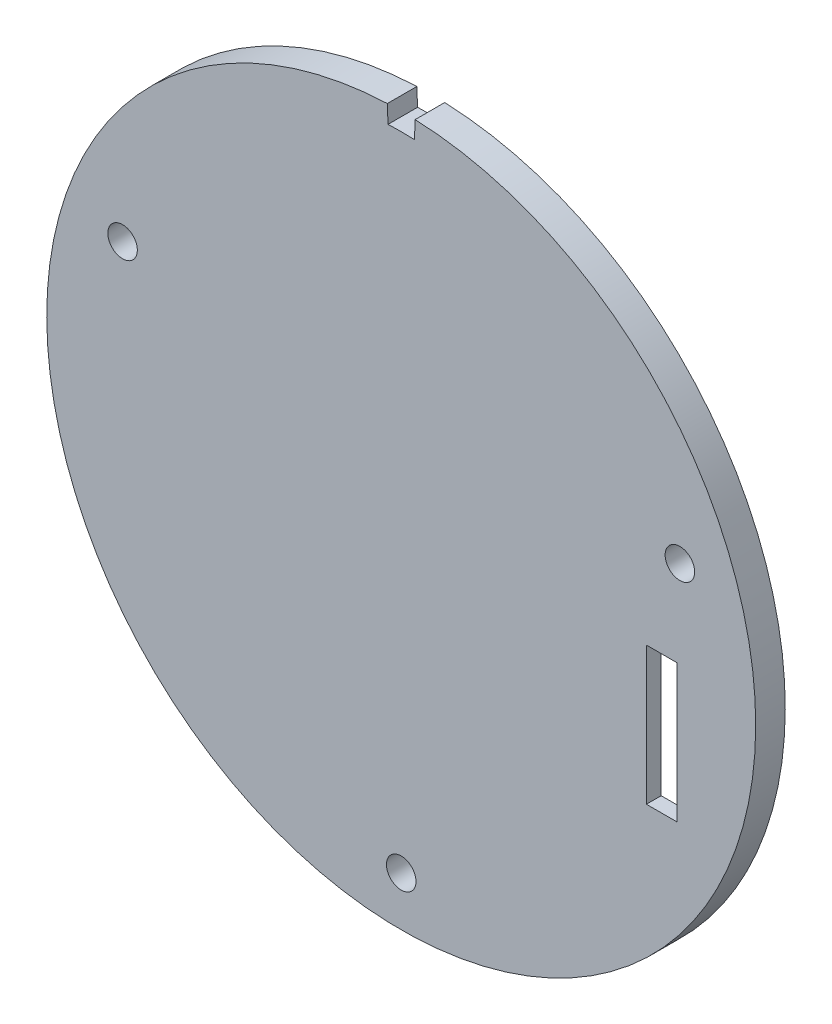
SolidWorks part; units mm, degrees
material "PMMA"
ref_plane "Front Plane" through (0, 0, 0) normal (0, 0, 1) x (1, 0, 0)
ref_plane "Top Plane" through (0, 0, 0) normal (0, 1, 0) x (1, 0, 0)
ref_plane "Right Plane" through (0, 0, 0) normal (1, 0, 0) x (0, 0, -1)
sketch "Sketch1" plane through (0, 0, 0) normal (0, 0, 1) x (1, 0, 0)
  line L0 (0, 45.9969) -> (0, -49.8146) construction
  line L1 (-28, 4.5) -> (28, 4.5)
  line L2 (28, 4.5) -> (28, -17)
  line L3 (28, -17) -> (21.5, -23.5)
  line L4 (21.5, -23.5) -> (-21.5, -23.5)
  line L5 (-21.5, -23.5) -> (-28, -17)
  line L6 (-28, -17) -> (-28, 4.5)
  line L7 (-1.4134, 35.9722) -> (-1.3427, 34.1736)
  line L8 (28, 1.5) -> (24.9, 1.5)
  line L9 (1.3427, 34.1736) -> (1.4134, 35.9722)
  line L10 (24.9, 1.5) -> (24.9, -12.5)
  line L11 (24.9, -12.5) -> (28, -12.5)
  line L12 (28.3, 10.3761) -> (-28.3, 10.3761) construction
  line L14 (23.5, -21.6239) -> (-23.5, -21.6239) construction
  line L15 (23.5, -21.6239) -> (23.5, 25.3761) construction
  line L16 (23.5, 25.3761) -> (-23.5, 25.3761) construction
  line L17 (-23.5, -21.6239) -> (-23.5, 25.3761) construction
  line L18 (23.5, -21.6239) -> (-23.5, 25.3761) construction
  line L19 (23.5, 25.3761) -> (-23.5, -21.6239) construction
  arc A0 (-1.4134, 35.9722) -> (1.4134, 35.9722) centre (0, 0) ccw
  arc A1 (-1.3427, 34.1736) -> (1.3427, 34.1736) centre (0, 0) cw
  circle A2 centre (28.3, 10.3761) radius 1.5
  circle A3 centre (-28.3, 10.3761) radius 1.5
  circle A4 centre (0, -31) radius 1.5
  point P22 (0, 1.8761)
  point P27 (-1.2692, -29.9126)
  dimension "D1" = 72
  dimension "D9" = 34.2
  dimension "D10" = 3
  dimension "D13" = 3
  dimension "D14" = 3
  dimension "D18" = 3
  dimension "D19" = 31
  dimension "D2" = 56
  dimension "D3" = 21.5
  dimension "D4" = 135
  dimension "D5" = 28
  dimension "D6" = 135
  dimension "D7" = 4.5
  dimension "D8" = 4.5
  dimension "D11" = 17
  dimension "D12" = 3.1
  dimension "D15" = 47
  dimension "D16" = 47
  dimension "D17" = 15
extrude "Boss-Extrude3" add sketch "Sketch1" against normal blind 3 contours A1 L0 L1 L2 L3 L4 A0 L9 | L0 A1 L7 A0 L4 L5 L6 L1 region at (0, 5.514, 0)
extrude "Boss-Extrude4" add sketch "Sketch1<9>" against normal blind 1.5 contours L1 L0 L4 L3 L2 L11 L10 L8 | L0 L1 L6 L5 L4 region at (-0.7744, -9.2798, 0)
sketch "Sketch1<9>" plane through (0, 0, 0) normal (0, 0, 1) x (1, 0, 0) same geometry as "Sketch1"
